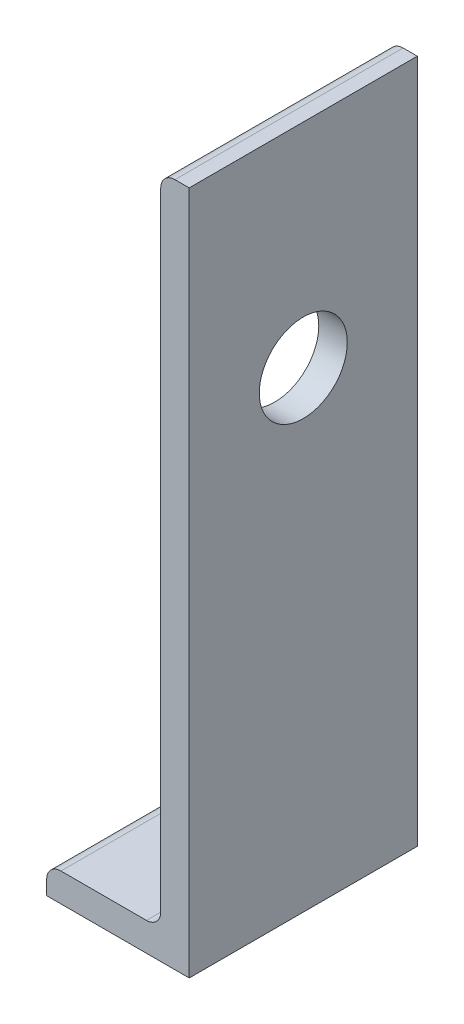
SolidWorks part; units mm, degrees
ref_plane "Front Plane" through (0, 0, 0) normal (0, 0, 1) x (1, 0, 0)
ref_plane "Top Plane" through (0, 0, 0) normal (0, 1, 0) x (1, 0, 0)
ref_plane "Right Plane" through (0, 0, 0) normal (1, 0, 0) x (0, 0, -1)
sketch "Sketch2" plane through (0, 0, 0) normal (0, 0, 1) x (1, 0, 0)
  line L0 (-15.875, 0) -> (15.875, 0)
  line L1 (15.875, 0) -> (15.875, 152.4)
  line L2 (15.875, 152.4) -> (9.525, 152.4) construction
  line L3 (9.525, 149.225) -> (9.525, 9.525)
  line L4 (6.35, 6.35) -> (-12.7, 6.35)
  line L5 (-15.875, 0) -> (-15.875, 6.35) construction
  line L6 (12.7, 152.4) -> (15.875, 152.4)
  line L7 (-15.875, 3.175) -> (-15.875, 0)
  arc A0 (9.525, 149.225) -> (12.7, 152.4) centre (12.7, 149.225) cw
  arc A1 (-15.875, 3.175) -> (-12.7, 6.35) centre (-12.7, 3.175) cw
  arc A2 (9.525, 9.525) -> (6.35, 6.35) centre (6.35, 9.525) cw
  dimension "Vert" = 152.4
  dimension "Horz" = 31.75
  dimension "Thickness" = 6.35
extrude "Boss-Extrude1" add sketch "Sketch2" along normal mid plane 50.8
ref_plane "Contact Plane 1" through (0, 6.35, 0) normal (0, 1, 0) x (1, 0, 0)
ref_plane "Contact Plane 2" through (9.525, 0, 0) normal (-1, 0, 0) x (0, 0, 1)
sketch "Sketch3" plane through (0, 0, 0) normal (0, -1, 0) x (1, 0, 0)
  line L0 (15.875, 0) -> (-15.875, 0) construction
  line L1 (15.875, 25.4) -> (15.875, -25.4) construction
  line L2 (-15.875, 25.4) -> (-15.875, -25.4) construction
  circle A0 centre (-4.826, 0) radius 4.765
  dimension "D1" = 9.53
  dimension "D2" = 20.701
extrude "Cut-Extrude1" cut sketch "Sketch3" against normal through all contours A0
sketch "Sketch5" plane through (15.875, 0, 0) normal (1, 0, 0) x (0, 0, -1)
  line L0 (-25.4, 0) -> (-25.4, 152.4) construction
  circle A0 centre (0, 105) radius 9.8
  dimension "D1" = 25.4
  dimension "D2" = 105
  dimension "D3" = 19.6
extrude "Cut-Extrude2" cut sketch "Sketch5" against normal blind 12.7
